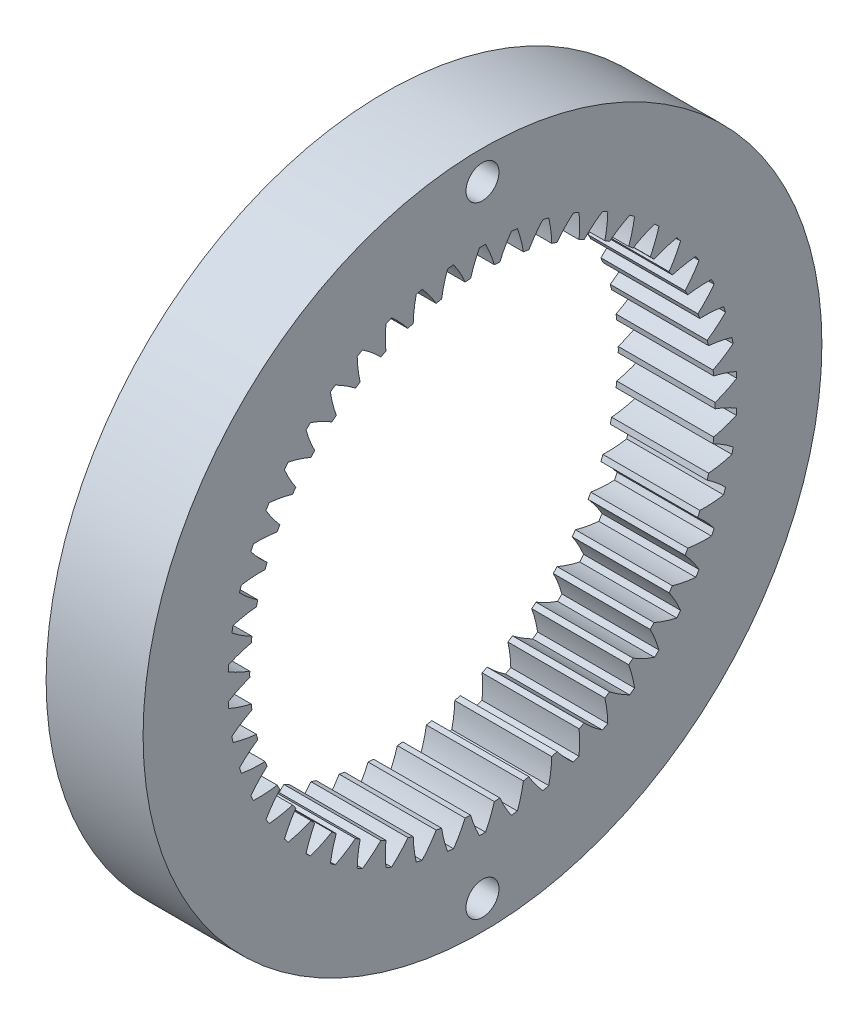
SolidWorks part; units mm, degrees
ref_plane "Plane1" through (0, 0, 0) normal (0, 0, 1) x (1, 0, 0)
ref_plane "Plane2" through (0, 0, 0) normal (0, 1, 0) x (1, 0, 0)
ref_plane "Plane3" through (0, 0, 0) normal (1, 0, 0) x (0, 0, -1)
sketch "HoldingSke" plane through (0, 0, 0) normal (0, 1, 0) x (1, 0, 0)
  line L0 (0, 0) -> (0.6428, -0.766)
  line L1 (-15, 0) -> (100, 0) construction
  line L2 (0, 0) -> (-2.1039, 2.3779)
  line L3 (0, 0) -> (-11.863, 4.5341)
  line L4 (0, 0) -> (5.5511, 6.6156)
  line L5 (0, 0) -> (-23.7986, -8.8762)
  line L6 (0, 0) -> (-10.5278, -7.1032)
  line L7 (-2.1039, 2.3779) -> (3.3635, 27.1825)
  line L8 (-76.2, 3.3779) -> (-54.61, 3.3779)
  line L9 (-71.009, 38.7566) -> (-53.1078, 45.2721)
  line L10 (-76.2, 71.12) -> (104.1128, 71.12)
  line L11 (0, 0) -> (-10, 0)
  line L12 (-76.2, 101.6) -> (-76.162, 101.6)
  line L13 (24.9733, 27.94) -> (52.9518, 28.4284)
  line L14 (24.9733, 27.94) -> (24.9743, 27.94)
  line L15 (24.9733, 27.94) -> (100.4006, 29.5858)
  circle A0 centre (0, 0) radius 35
  circle A1 centre (0, 0) radius 12.7
  circle A2 centre (0, 0) radius 12.7
  dimension "Num_teeth" = 50
  dimension "Pitch_radius" = 180.3128
  dimension "Width" = 10
  dimension "Diameter" = 70
sketch "BasProSke" plane through (0, 0, 0) normal (0, 1, 0) x (1, 0, 0)
  line L0 (-10, 0) -> (60, 0) construction
  line L1 (0, 24) -> (0, 35)
  line L2 (0, 24) -> (10, 24)
  line L3 (10, 24) -> (10, 35)
  line L4 (10, 35) -> (0, 35)
  dimension "Thickness" = 10
  dimension "Diameter" = 70
revolve "Base-Revolve" add sketch "BasProSke" angle 360 about L0
sketch "TooCutSke" plane through (0, 0, 0) normal (1, 0, 0) x (0, 0, -1)
  line L3 (0.8803, 24.9845) -> (0.8803, 53.6633) construction
  line L4 (0, 0) -> (0, 59.563) construction
  line L5 (0, 0) -> (-4.2903, 68.1927) construction
  line L6 (-10.7899, 20.506) -> (36.4405, 23.4775) construction
  circle A0 centre (0, 0) radius 25 construction
  circle A1 centre (0, 0) radius 26.251 construction
  circle A2 centre (0, 0) radius 21.1431 construction
  circle A3 centre (0, 0) radius 23.9746 construction
  arc A4 (1.2282, 23.9431) -> (0.3126, 26.2491) centre (-10.7899, 20.506) ccw
  arc A5 (1.2282, 23.9431) -> (-1.2282, 23.9431) centre (0, 0) ccw
  arc A6 (0.3126, 26.2491) -> (-0.3126, 26.2491) centre (0, 0) ccw
  arc A7 (-0.3126, 26.2491) -> (-1.2282, 23.9431) centre (10.7899, 20.506) ccw
extrude "ToothCut" cut sketch "TooCutSke" along normal through all
fillet "Breaks" [suppressed] radius 0.1
fillet "RootFillets" [suppressed] radius 0.251
pattern_circular "TeethCuts" count 50 every 7.2 about axis through (-10, 0, 0) along (1, 0, 0) of "RootFillets", "Breaks", "ToothCut"
sketch "Croquis2" plane through (0, 0, 0) normal (-1, 0, 0) x (0, 0, 1)
  line L0 (0, 0) -> (11.5172, 0) construction
  circle A0 centre (0, 0) radius 25 construction
  circle A1 centre (0, -32) radius 1.7
  circle A2 centre (0, 0) radius 32 construction
  circle A3 centre (0, 32) radius 1.7
  circle A4 centre (0, 0) radius 35 construction
  point P13 (0, 0)
  dimension "D1" = 50
  dimension "D2" = 3
  dimension "D3" = 3.4
extrude "Cortar-Extruir1" cut sketch "Croquis2" against normal up to surface (10 mm away) up to face at (10, 0, 35)
equation "' \"Module@HoldingSke\" = 6.35"
equation "' \"Num_teeth@HoldingSke\" = 24"
equation "' \"Ap@HoldingSke\" =  14.5"
equation "' \"Ap@HoldingSke\" = 14.5"
equation "' \"Width@HoldingSke\" = 12"
equation "' \"Diameter@HoldingSke\" = 8 * 25.4"
equation "' \"Show_teeth@HoldingSke\" = 100"
equation "' \"Backlash@HoldingSke\" = 0.009 * 25.4"
equation "' \"Addendum_fac@HoldingSke\" = 1.0"
equation "' \"Dedendum_fac@HoldingSke\" = 1.25"
equation "' \"Dedendum_add@HoldingSke\" = 0.00005 * 25.4"
equation "' \"Clearance_fac@HoldingSke\" = 0.25"
equation "\"Pitch@HoldingSke\" = 1 / \"Module@HoldingSke\" "
equation "\"Overcut_dia@TooCutSke\" = (\"Num_teeth@HoldingSke\" - 2 * \"Addendum_fac@HoldingSke\") / \"Pitch@HoldingSke\" - 0.002 * 25.4"
equation "\"Pitch_dia@TooCutSke\" = \"Num_teeth@HoldingSke\" / \"Pitch@HoldingSke\""
equation "\"Base_dia@TooCutSke\" = \"Num_teeth@HoldingSke\" / \"Pitch@HoldingSke\" * cos((\"Ap@HoldingSke\"  * 3.14159265 / 180)) * 0.90"
equation "\"Root_dia@TooCutSke\" = \"Num_teeth@HoldingSke\"  / \"Pitch@HoldingSke\" + 2 *  \"Dedendum_fac@HoldingSke\"/ \"Pitch@HoldingSke\" + \"Dedendum_add@HoldingSke\" * 2"
equation "\"Half_ang@TooCutSke\" = 180 / \"Num_teeth@HoldingSke\""
equation "\"Half_CT@TooCutSke\" = \"Num_teeth@HoldingSke\" / \"Pitch@HoldingSke\" * sin((3.14159265 / 2 / \"Num_teeth@HoldingSke\")) / 2 + 10 * \"Backlash@HoldingSke\" / 4"
equation "\"Flank_rad@TooCutSke\" = \"Num_teeth@HoldingSke\" / \"Pitch@HoldingSke\" / 4"
equation "\"Radius@RootFillets\"= \"Clearance_fac@HoldingSke\" / \"Pitch@HoldingSke\" + \"Dedendum_add@HoldingSke\""
equation "\"Break_rad@Breaks\" = 0.02 / \"Pitch@HoldingSke\" * 5"
equation "\"Num_teeth@TeethCuts\" = int( \"Show_teeth@HoldingSke\" ) + 1"
equation "\"Num_teeth@TeethCuts\" = ((sgn( \"Num_teeth@TeethCuts\" - \"Num_teeth@HoldingSke\" )-1)*( \"Num_teeth@TeethCuts\" - \"Num_teeth@HoldingSke\" ))/-2+ \"Num_teeth@HoldingSke\""
equation "\"Num_teeth@TeethCuts\" = ((sgn( \"Num_teeth@TeethCuts\" - 2.0)+1)*( \"Num_teeth@TeethCuts\" - 2.0))/2 +2.0"
equation "\"Angle@TeethCuts\" = 360.0 / \"Num_teeth@HoldingSke\""
equation "\"Diameter@BasProSke\" = \"Num_teeth@HoldingSke\"  / \"Pitch@HoldingSke\" + 2 *  \"Dedendum_fac@HoldingSke\"/ \"Pitch@HoldingSke\" + \"Dedendum_add@HoldingSke\" * 2 + 0.002 * 25.4"
equation "\"Diameter@BasProSke\" = ((sgn( \"Diameter@BasProSke\"  - \"Diameter@HoldingSke\" )+1)*( \"Diameter@BasProSke\"  - \"Diameter@HoldingSke\" ))/2 + \"Diameter@HoldingSke\""
equation "\"Inside_diameter@BasProSke\" =  (\"Num_teeth@HoldingSke\" - 2 * \"Addendum_fac@HoldingSke\") / \"Pitch@HoldingSke\" "
equation "\"Thickness@BasProSke\"  = \"Width@HoldingSke\""
